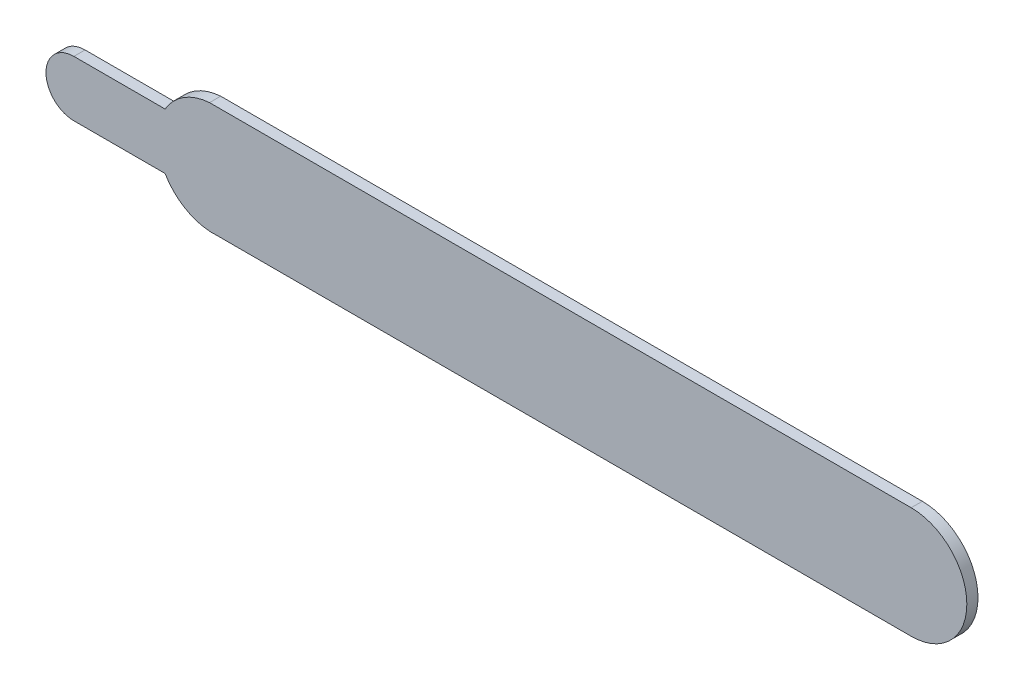
SolidWorks part; units mm, degrees
ref_plane "Front Plane" through (0, 0, 0) normal (0, 0, 1) x (1, 0, 0)
ref_plane "Top Plane" through (0, 0, 0) normal (0, 1, 0) x (1, 0, 0)
ref_plane "Right Plane" through (0, 0, 0) normal (1, 0, 0) x (0, 0, -1)
sketch "Sketch1" plane through (0, 0, 0) normal (0, 0, 1) x (1, 0, 0)
  line L0 (0, 0) -> (125, 0) construction
  line L1 (-0.7033, 9.9752) -> (125, 9.9744)
  line L2 (0.7255, -9.9736) -> (125.016, -9.9744)
  line L3 (0, 0) -> (-25, 0) construction
  line L8 (-8.6603, -5) -> (-25, -5)
  line L9 (-8.6603, 5) -> (-25, 5)
  arc A0 (-0.7033, 9.9752) -> (-8.6603, 5) centre (0, 0) ccw
  arc A1 (125.016, -9.9744) -> (125, 9.9744) centre (125, 0) ccw
  arc A3 (-25, 5) -> (-25, -5) centre (-25, 0) ccw
  arc A4 (-8.6603, -5) -> (0.7255, -9.9736) centre (0, 0) ccw
  point P3 (50, 0)
  point P8 (119.1468, 10)
  point P10 (-12.5, 0)
  point P11 (125, 9.9752)
  point P15 (0, 0)
  dimension "D1" = 10
  dimension "D3" = 5
  dimension "D2" = 125
  dimension "D4" = 25
extrude "Boss-Extrude1" add sketch "Sketch1" along normal mid plane 2
